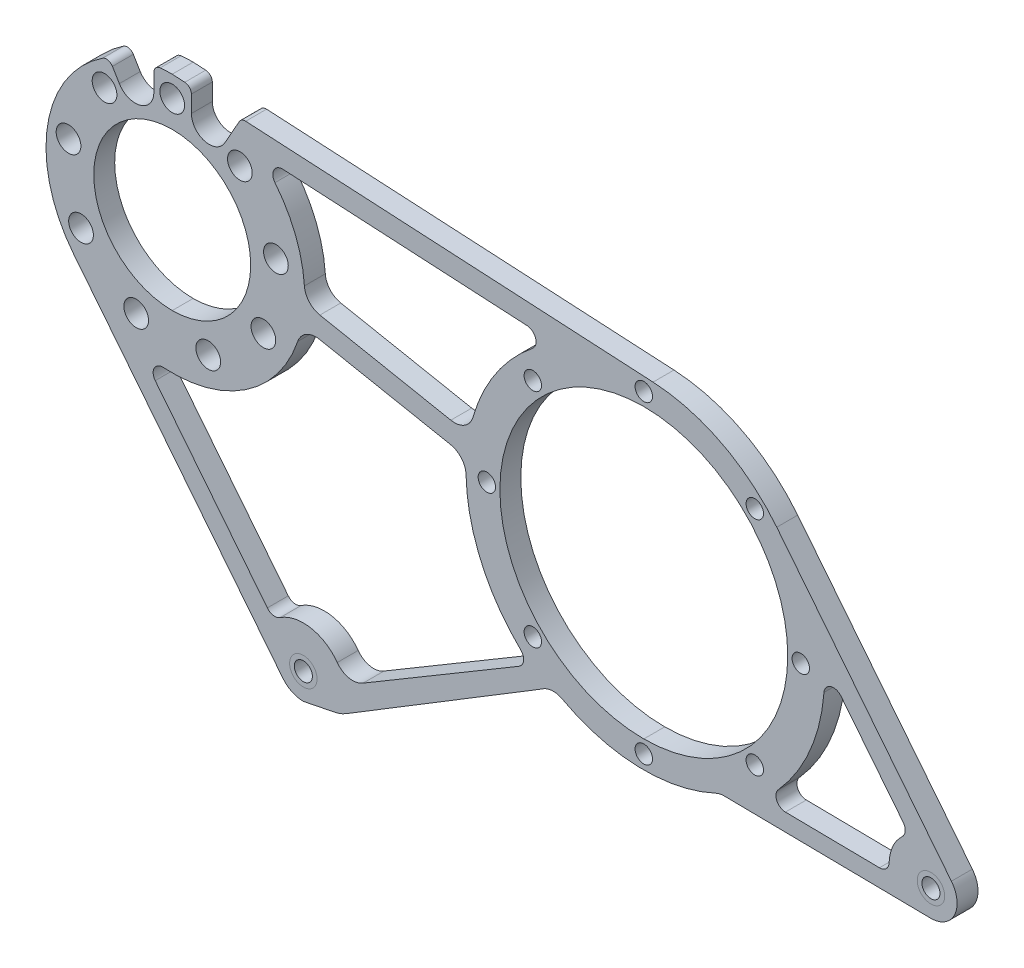
SolidWorks part; units mm, degrees
material "6061-T6 (SS)"
ref_plane "Front Plane" through (0, 0, 0) normal (0, 0, 1) x (1, 0, 0)
ref_plane "Top Plane" through (0, 0, 0) normal (0, 1, 0) x (1, 0, 0)
ref_plane "Right Plane" through (0, 0, 0) normal (1, 0, 0) x (0, 0, -1)
sketch "Sketch1" plane through (0, 0, 0) normal (0, 0, 1) x (1, 0, 0)
  line L0 (0, 0) -> (171.7726, -25.4) construction
  line L1 (47.761, -127.9853) -> (276.361, -82.1437)
  line L2 (0, 45.974) -> (175.1446, 36.4206)
  line L3 (-35.96, -28.6441) -> (40.3107, -124.3949)
  line L4 (220.1994, 13.1746) -> (283.8113, -66.6841)
  line L5 (171.7726, 36.5125) -> (171.7726, 27.0256) construction
  line L6 (0, 28.575) -> (0, 45.974) construction
  circle A0 centre (0, 0) radius 45.974
  circle A1 centre (171.7726, -25.4) radius 61.9125
  circle A2 centre (171.7726, -25.4) radius 52.4256
  circle A3 centre (0, 0) radius 28.575
  circle A4 centre (47.761, -118.4603) radius 9.525
  circle A5 centre (276.361, -72.6187) radius 9.525
  circle A6 centre (47.761, -118.4603) radius 3.2995
  circle A7 centre (276.361, -72.6187) radius 3.2995
  circle A19 centre (171.7726, -25.4) radius 57.1691 construction
  circle A21 centre (0, 0) radius 38.354 construction
  point P23 (0, 38.354)
  point P44 (0, 0)
  point P47 (171.7726, 31.7691)
  dimension "D1" = 91.948
  dimension "D2" = 123.825
  dimension "D5" = 104.8512
  dimension "D6" = 57.15
  dimension "D7" = 6.5989
  dimension "D8" = 6.5989
  dimension "D9" = 228.6
  dimension "D10" = 19.05
  dimension "D11" = 19.05
  dimension "D14" = 7.62
  dimension "D3" = 171.7726
  dimension "D4" = 25.4
  dimension "D12" = 117.2
  dimension "D13" = 76.2
extrude "Boss-Extrude1" add sketch "Sketch1" along normal blind 7.62 contours A5 L4 A1 L2 A0 L3 A4 L1 | L2 A0 A3 | A4 L1 A6 | A5 A7 | A1 A2 region at (43.7428, -126.7982, 0) region at (104.2025, -48.9688, 0) region at (268.0231, -68.6005, 0) region at (-40.2441, 19.3945, 0) region at (228.5635, -5.5459, 0)
sketch "Sketch2" plane through (0, 0, 7.62) normal (0, 0, 1) x (1, 0, 0)
  line L0 (171.7726, 36.5125) -> (171.7726, 27.0256) construction
  circle A0 centre (0, 38.354) radius 4.4996
  circle A1 centre (171.7726, 31.7691) radius 3.175
  circle A2 centre (24.6535, 29.3809) radius 4.4996
  circle A3 centre (37.7713, 6.6601) radius 4.4996
  circle A4 centre (33.2155, -19.177) radius 4.4996
  circle A5 centre (13.1178, -36.041) radius 4.4996
  circle A6 centre (-13.1178, -36.041) radius 4.4996
  circle A7 centre (-33.2155, -19.177) radius 4.4996
  circle A8 centre (-37.7713, 6.6601) radius 4.4996
  circle A9 centre (-24.6535, 29.3809) radius 4.4996
  circle A10 centre (0, 0) radius 38.354 construction
  circle A22 centre (212.1972, 15.0246) radius 3.175
  circle A23 centre (228.9416, -25.4) radius 3.175
  circle A24 centre (212.1972, -65.8246) radius 3.175
  circle A25 centre (171.7726, -82.5691) radius 3.175
  circle A26 centre (131.348, -65.8246) radius 3.175
  circle A27 centre (114.6035, -25.4) radius 3.175
  circle A28 centre (131.348, 15.0246) radius 3.175
  circle A33 centre (171.7726, -25.4) radius 57.169 construction
  point P26 (0, 0)
  point P28 (0, 0)
  point P43 (171.7726, -25.4)
  point P44 (0, 0)
  point P45 (0, 0)
  point P48 (171.7726, -25.4)
  dimension "D1" = 8.9992
  dimension "D2" = 6.35
  dimension "D3" = 9
  dimension "D4" = 8
extrude "Cut-Extrude1" cut sketch "Sketch2" against normal through all both and the other way through all
ref_plane "Plane1" through (2.54, 0, 0) normal (1, 0, 0) x (0, 0, -1)
ref_plane "Plane2" through (171.7726, 0, 0) normal (1, 0, 0) x (0, 0, -1)
split line "Split Line5"
sketch "Sketch1<4>" plane through (0, 0, 0) normal (0, 0, 1) x (1, 0, 0) same geometry as "Sketch1"
sketch "Sketch4" plane through (0, 0, 7.62) normal (0, 0, 1) x (1, 0, 0)
  circle A0 centre (276.361, -72.6187) radius 3.2995
  circle A1 centre (276.361, -72.6187) radius 5
  circle A2 centre (47.761, -118.4603) radius 3.2995
  circle A3 centre (47.761, -118.4603) radius 5
  dimension "D1" = 10
  dimension "D2" = 6.5989
split line "Split Line6"
split line "Split Line7"
split line "Split Line8"
sketch "Sketch5" plane through (0, 0, 0) normal (0, 0, -1) x (-1, 0, 0)
  line L1 (-266.229, -56.8414) -> (-243.59, -28.4202)
  line L2 (-257.604, -75.5493) -> (-223.3455, -75.1038)
  line L3 (-129.2329, 31.2936) -> (-40.3109, 36.1439)
  line L4 (-101.4745, -12.4239) -> (-53.7801, -3.115)
  line L6 (-34.6489, -105.0569) -> (6.1866, -53.7918)
  line L7 (-101.374, -20.168) -> (-53.6667, -10.8566)
  line L8 (0, 45.974) -> (-175.1446, 36.4206) construction
  line L9 (35.96, -28.6441) -> (-40.3107, -124.3949) construction
  line L11 (-220.1994, 13.1746) -> (-283.8113, -66.6841) construction
  line L12 (-171.7726, -25.4) -> (-171.7726, 974.6) construction
  line L15 (-51.4334, -127.2489) -> (-276.361, -82.1437) construction
  line L16 (-69.5282, -111.3406) -> (-126.3022, -77.645)
  line L17 (-201.074, -81.1647) -> (-276.361, -82.1437)
  line L18 (-276.361, -82.1437) -> (-61.4054, -125.2492)
  line L19 (-134.6203, -80.6651) -> (-61.4054, -125.2492)
  arc A0 (-265.8966, -61.5393) -> (-261.1275, -72.1718) centre (-276.361, -72.6187) cw
  arc A1 (-37.423, 30.4721) -> (-48.1492, 3.2677) centre (0, 0) ccw
  arc A2 (-131.222, 25.1055) -> (-109.5255, -7.4987) centre (-171.7726, -25.4) cw
  arc A3 (-61.4054, -125.2492) -> (-39.3022, -105.7833) centre (-47.761, -118.4603) cw
  arc A4 (-126.9351, -72.1414) -> (-107.0192, -26.8656) centre (-171.7726, -25.4) ccw
  arc A5 (3.2317, -48.1517) -> (-45.7124, -15.4728) centre (0, 0) cw
  arc A6 (-237.3981, -30.3277) -> (-220.7984, -69.3029) centre (-171.7726, -25.4) ccw
  arc A7 (-265.8966, -61.5393) -> (-266.229, -56.8414) centre (-263.5072, -59.0095) cw
  arc A8 (-261.1275, -72.1718) -> (-257.604, -75.5493) centre (-257.6492, -72.0697) ccw
  arc A9 (-223.3455, -75.1038) -> (-220.7984, -69.3029) centre (-223.3907, -71.6243) ccw
  arc A10 (-243.59, -28.4202) -> (-237.3981, -30.3277) centre (-240.8681, -30.5883) cw
  arc A11 (-39.3022, -105.7833) -> (-34.6489, -105.0569) centre (-37.3707, -102.8888) ccw
  arc A14 (6.1866, -53.7918) -> (3.2317, -48.1517) centre (3.4647, -51.6237) ccw
  arc A15 (-45.7124, -15.4728) -> (-53.6667, -10.8566) centre (-52.3286, -17.7123) ccw
  arc A16 (-107.0192, -26.8656) -> (-101.374, -20.168) centre (-100.036, -27.0237) cw
  arc A17 (-109.5255, -7.4987) -> (-101.4745, -12.4239) centre (-102.8126, -5.5682) ccw
  arc A18 (-48.1492, 3.2677) -> (-53.7801, -3.115) centre (-55.1182, 3.7406) cw
  arc A19 (-40.3109, 36.1439) -> (-37.423, 30.4721) centre (-40.1214, 32.6692) cw
  arc A20 (-129.2329, 31.2936) -> (-131.222, 25.1055) centre (-129.0434, 27.8189) ccw
  arc A21 (-142.131, -80.117) -> (-198.0354, -81.8167) centre (-171.7726, -25.4) cw
  arc A22 (-126.3022, -77.645) -> (-126.9351, -72.1414) centre (-124.5262, -74.6526) cw
  arc A23 (-198.0354, -81.8167) -> (-201.074, -81.1647) centre (-200.9832, -88.1491) ccw
  arc A24 (-134.6203, -80.6651) -> (-142.131, -80.117) centre (-138.8038, -86.2587) ccw
  arc A25 (-69.5282, -111.3406) -> (-60.1156, -109.5373) centre (-65.7782, -105.4476) ccw
  point P24 (-133.076, -82.6428)
  point P32 (0, 0)
  point P33 (-276.361, -82.1437)
  point P41 (-268.4302, -59.6048)
  point P44 (-291.2242, -75.9864)
  point P47 (-215.0307, -74.9957)
  point P50 (-237.4123, -20.6647)
  point P52 (-140.5397, -82.142)
  point P53 (-57.8333, -107.0233)
  point P60 (-57.8333, -107.0233)
  point P61 (0, 0)
  point P62 (-58.9983, -108.1657)
  point P63 (-67.3672, -110.1028)
  point P65 (-70.9663, -107.2153)
  point P66 (-57.324, -106.5941)
  point P67 (-60.2029, -109.6594)
  point P68 (-70.088, -110.5728)
  point P72 (-69.4642, -110.7327)
  point P74 (-69.5282, -111.3406)
  point P75 (-132.793, -81.7219)
  point P80 (-47.293, -9.6126)
  point P83 (-107.133, -21.292)
  point P92 (-134.6203, -80.6651)
  point P93 (-208.4666, -95.7587)
  point P94 (-276.361, -82.1441)
  point P95 (-211.8604, -87.3064)
  point P96 (-209.0867, -81.1119)
  point P97 (-212.9738, -87.0831)
  point P98 (-211.1762, -83.6302)
  point P99 (0, 0)
  point P100 (-276.361, -82.1437)
  line M26 (-276.361, -82.1437) -> (-51.4334, -127.2489)
  dimension "D1" = 15.24
  dimension "D7" = 3.4798
  dimension "D8" = 15.24
  dimension "D11" = 64.77
  dimension "D13" = 64.77
  dimension "D14" = 48.26
  dimension "D15" = 3.4798
  dimension "D16" = 48.26
  dimension "D17" = 7.62
  dimension "D18" = 6.985
  dimension "D19" = 3.4798
  dimension "D20" = 0.65
  dimension "D10" = 3.4798
  dimension "D23" = 6.985
  dimension "D24" = 6.985
  dimension "D26" = 6.985
  dimension "D29" = 66.0203
  dimension "D30" = 86.632
  dimension "D31" = 62.23
  dimension "D2" = 49.784
  dimension "D3" = 76.2
  dimension "D4" = 7.62
  dimension "D5" = 6.35
  dimension "D9" = 7.62
  dimension "D12" = 7.62
  dimension "D25" = 20
  dimension "D27" = 85.7214
  dimension "D28" = 0
extrude "Cut-Extrude2" cut sketch "Sketch5" against normal through all both and the other way through all contours L16 A25 A3 A11 L6 A14 A5 A15 L7 A16 A4 A22 | L19 A24 A21 A23 L17 M26 | L3 A20 A2 A17 L4 A18 A1 A19 | A10 L1 A7 A0 A8 L2 A9 A6 region at (244.5472, -57.2693, 0) region at (83.052, 14.7275, 0) region at (64.0038, -61.6283, 0) region at (156.4454, -96.96, 0)
fillet "Fillet2" radius 12.7 1 edges at (61.4054, -125.2492, 3.81)
sketch "Sketch6" plane through (0, 0, 0) normal (0, 0, -1) x (-1, 0, 0)
  line L0 (-19.1496, 33.8712) -> (-24.6535, 29.3809) construction
  line L1 (-6.9836, 37.0561) -> (0, 38.354) construction
  line L2 (-19.1496, 33.8712) -> (-25.1805, 44.6005)
  line L3 (-5.0005, 45.7012) -> (-175.1446, 36.4206) construction
  line L4 (-6.9836, 37.0561) -> (-6.9836, 45.5931)
  line L5 (6.6943, 36.8702) -> (6.6943, 45.484)
  line L6 (19.2601, 33.3713) -> (23.1077, 39.7447)
  line L7 (-25.1805, 44.6005) -> (-6.9836, 45.5931)
  arc A0 (-6.9836, 37.0561) -> (-19.1496, 33.8712) centre (-13.4835, 37.0561) cw
  arc A1 (6.6943, 36.8702) -> (19.2601, 33.3713) centre (13.4643, 36.8702) ccw
  arc A2 (35.96, -28.6441) -> (0, 45.974) centre (0, 0) ccw construction
  arc A3 (6.6943, 45.484) -> (23.1077, 39.7447) centre (0, 0) cw
  point P5 (-11.8374, 30.7681)
  point P12 (11.6483, 30.3483)
  dimension "D1" = 6.4999
  dimension "D2" = 32.9667
  dimension "D3" = 32.5069
  dimension "D4" = 13.5458
  dimension "D5" = 13.5458
  dimension "D6" = 13.6779
  dimension "D7" = 7.4447
extrude "Cut-Extrude3" cut sketch "Sketch6" against normal through all both and the other way through all
fillet "Fillet3" radius 2.54 4 edges at (-6.6943, 45.484, 3.81) (-23.1077, 39.7447, 3.81) (25.1805, 44.6005, 3.81)
